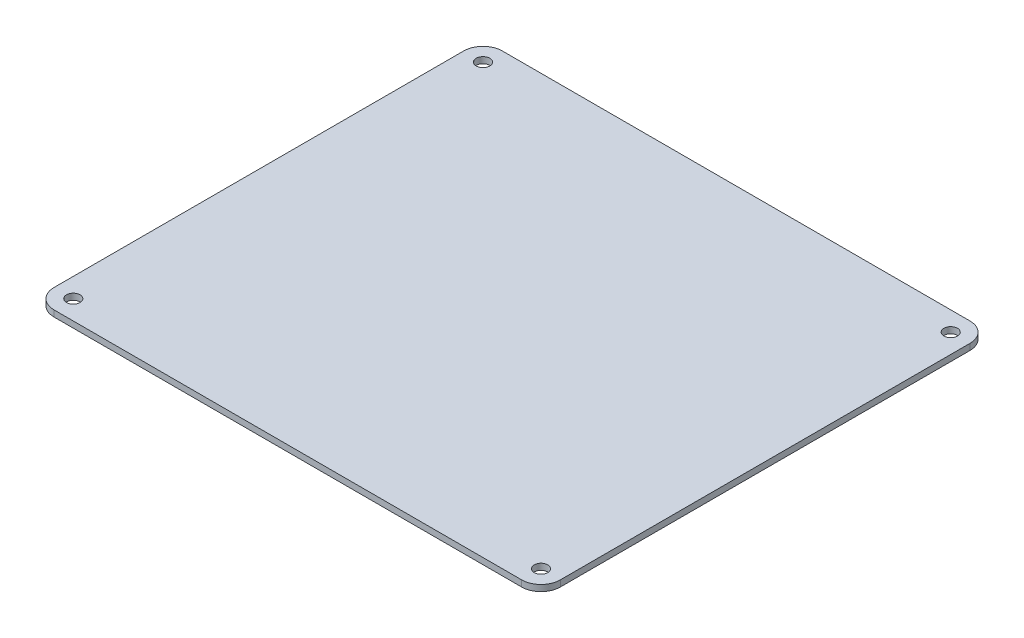
SolidWorks part; units mm, degrees
ref_plane "Plan de face" through (0, 0, 0) normal (0, 0, 1) x (1, 0, 0)
ref_plane "Plan de dessus" through (0, 0, 0) normal (0, 1, 0) x (1, 0, 0)
ref_plane "Plan de droite" through (0, 0, 0) normal (1, 0, 0) x (0, 0, -1)
sketch "Esquisse1" plane through (0, 0, 0) normal (0, 1, 0) x (1, 0, 0)
  line L0 (-65.5, 53) -> (-60.5, 53) construction
  line L1 (-60.5, 58) -> (60.5, 58)
  line L2 (-65.5, 53) -> (-65.5, -53)
  line L3 (-60.5, -58) -> (60.5, -58)
  line L4 (65.5, 53) -> (65.5, -53)
  line L5 (-65.5, 58) -> (65.5, -58) construction
  line L6 (-65.5, -58) -> (65.5, 58) construction
  line L7 (-60.5, 58) -> (-60.5, 53) construction
  line L8 (0, 0) -> (0, 58) construction
  line L9 (0, 0) -> (65.5, 0) construction
  circle A0 centre (-60.5, 53) radius 1.75
  circle A1 centre (60.5, 53) radius 1.75
  circle A2 centre (60.5, -53) radius 1.75
  circle A3 centre (-60.5, -53) radius 1.75
  arc A4 (-65.5, -53) -> (-60.5, -58) centre (-60.5, -53) ccw
  arc A5 (60.5, -58) -> (65.5, -53) centre (60.5, -53) ccw
  arc A6 (60.5, 58) -> (65.5, 53) centre (60.5, 53) cw
  arc A7 (-60.5, 58) -> (-65.5, 53) centre (-60.5, 53) ccw
  point P0 (0, 0)
  dimension "D5" = 3.5
  dimension "D6" = 5
  dimension "D1" = 116
  dimension "D2" = 131
  dimension "D3" = 5
  dimension "D4" = 5
extrude "Boss.-Extru.1" add sketch "Esquisse1" along normal mid plane 1.61
sketch "Esquisse3" plane through (0, -0.805, 0) normal (0, -1, 0) x (1, 0, 0)
  line L0 (65.5, -42) -> (23.5, -42) construction
  line L1 (65.5, 53) -> (65.5, -53) construction
  line L2 (23.5, -58) -> (23.5, -42) construction
  line L3 (60.5, -58) -> (-60.5, -58) construction
  circle A0 centre (23.5, -42) radius 0.225
  dimension "D3" = 0.45
  dimension "D1" = 42
  dimension "D2" = 16
extrude "Boss.-Extru.2" add sketch "Esquisse3" along normal blind 5
